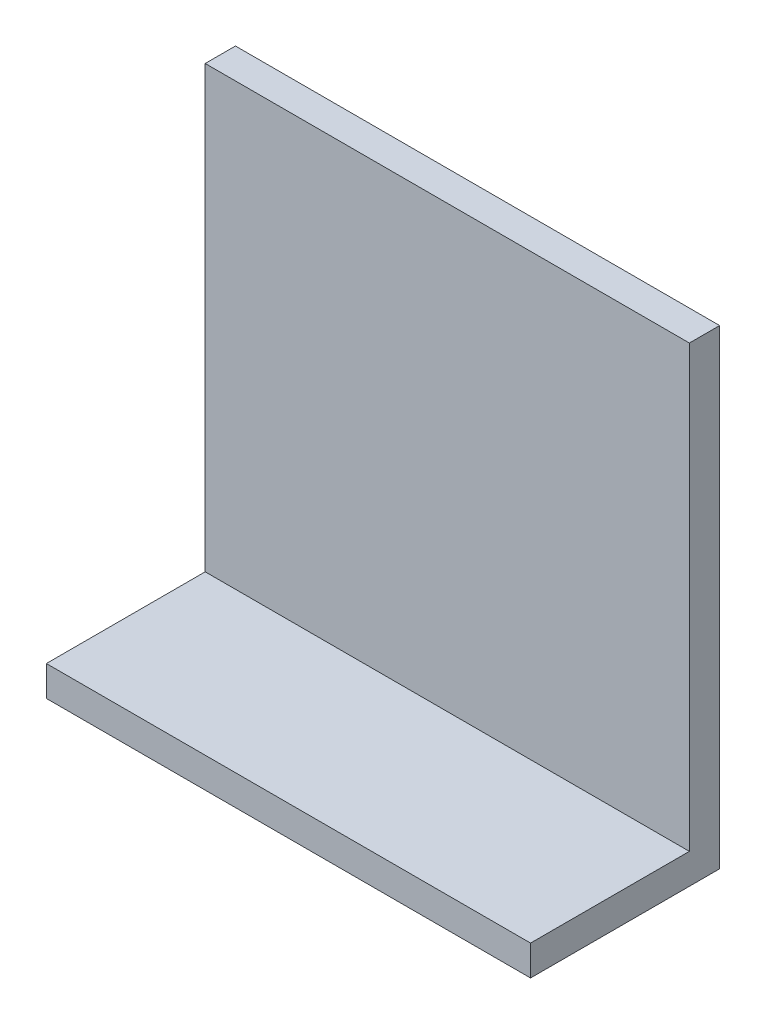
SolidWorks part; units mm, degrees
ref_plane "Front Plane" through (0, 0, 0) normal (0, 0, 1) x (1, 0, 0)
ref_plane "Top Plane" through (0, 0, 0) normal (0, 1, 0) x (1, 0, 0)
ref_plane "Right Plane" through (0, 0, 0) normal (1, 0, 0) x (0, 0, -1)
sketch "Sketch1" plane through (0, 0, 0) normal (0, 1, 0) x (1, 0, 0)
  line L1 (0, 0) -> (32.0076, 0)
  line L2 (0, 0) -> (0, 12.5)
  line L3 (0, 12.5) -> (32.0076, 12.5)
  line L4 (32.0076, 0) -> (32.0076, 12.5)
  dimension "D1" = 12.5
extrude "Boss-Extrude1" add sketch "Sketch1" along normal blind 2
sketch "Sketch2" plane through (0, 0, -12.5) normal (0, 0, -1) x (-1, 0, 0)
  line L1 (-32.0076, 2) -> (0, 2)
  line L2 (-32.0076, 2) -> (-32.0076, 31.1024)
  line L3 (-32.0076, 31.1024) -> (0, 31.1024)
  line L4 (0, 2) -> (0, 31.1024)
extrude "Boss-Extrude2" add sketch "Sketch2" against normal blind 2
